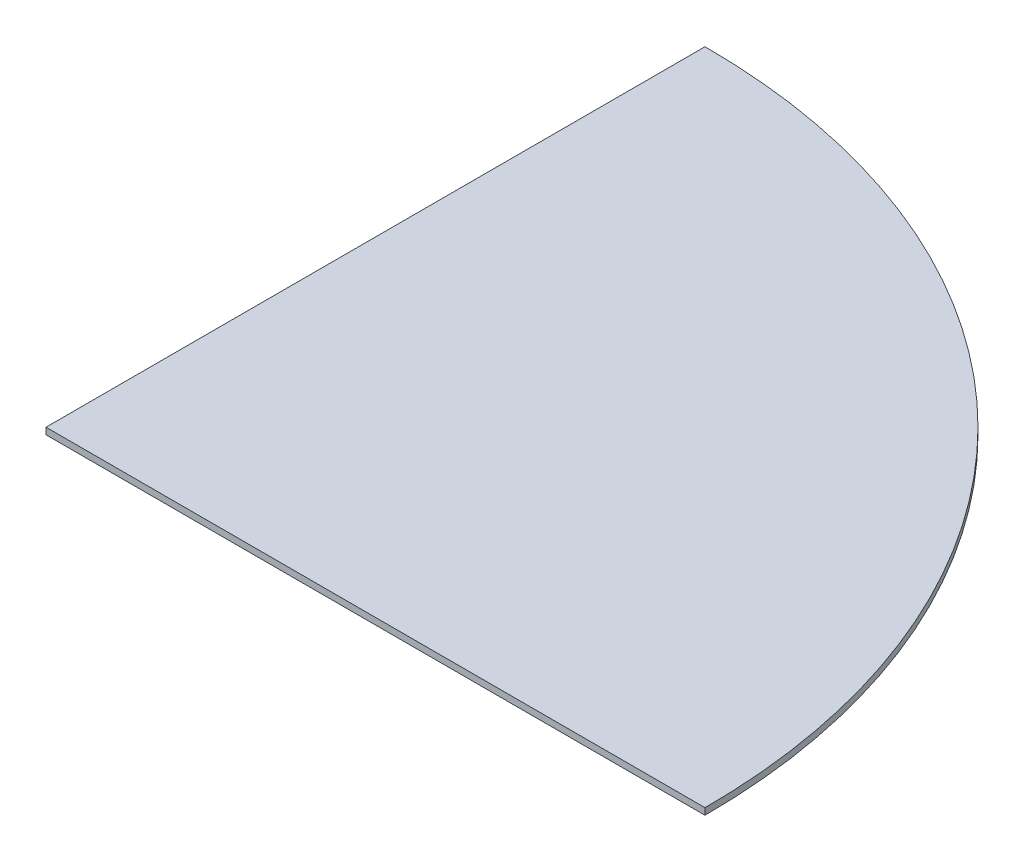
SolidWorks part; units mm, degrees
ref_plane "Front Plane" through (0, 0, 0) normal (0, 0, 1) x (1, 0, 0)
ref_plane "Top Plane" through (0, 0, 0) normal (0, 1, 0) x (1, 0, 0)
ref_plane "Right Plane" through (0, 0, 0) normal (1, 0, 0) x (0, 0, -1)
other "Configuration Table"
sketch "Sketch1" plane through (0, 0, 0) normal (0, 1, 0) x (1, 0, 0)
  line L0 (0, 0) -> (0, 1000)
  line L1 (0, 0) -> (1000, 0)
  arc A0 (0, 1000) -> (1000, 0) centre (0, 0) cw
sheet metal parameters "Sheet-Metal1" thickness 10 parameters "D1"=0.7366
base flange "Base-Flange1" sketch "Sketch1" thickness 10 reverse thickness direction yes parameters "D1"=0.7366
ref_axis "Axis1" through (0, 10, 0) along (0, -1, 0)
flat pattern "Flat-Pattern1" [suppressed]
sketch "Bend-Lines1" plane through (0, 0, 0) normal (0, 1, 0) x (-1, 0, 0)
